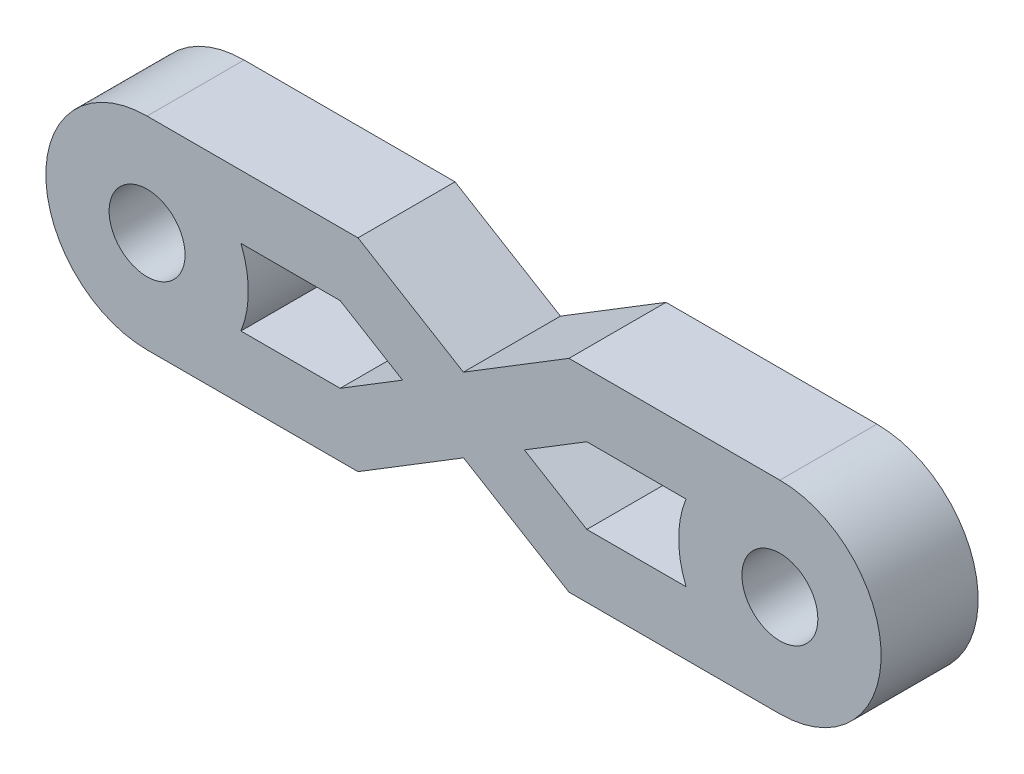
SolidWorks part; units mm, degrees
ref_plane "Front Plane" through (0, 0, 0) normal (0, 0, 1) x (1, 0, 0)
ref_plane "Top Plane" through (0, 0, 0) normal (0, 1, 0) x (1, 0, 0)
ref_plane "Right Plane" through (0, 0, 0) normal (1, 0, 0) x (0, 0, -1)
sketch "Sketch2" plane through (0, 0, 0) normal (0, 0, 1) x (1, 0, 0)
  line L0 (-117.2241, -4.8523) -> (-107.2241, -4.8523)
  line L1 (-87.2242, 4.8) -> (-97.2242, 4.8)
  line L2 (-97.2242, 4.8) -> (-102.2275, 1.7314)
  line L3 (-108.0708, -1.8523) -> (-112.7744, -1.8523)
  line L4 (-107.2241, -4.8523) -> (-102.2208, -1.7837)
  line L5 (-96.3775, 1.8) -> (-91.6739, 1.8)
  line L6 (-87.2242, -4.8) -> (-97.2242, -4.8)
  line L7 (-97.2242, -4.8) -> (-102.2208, -1.7837)
  line L8 (-108.0708, 1.7477) -> (-112.7744, 1.7477)
  line L9 (-117.2241, 4.7477) -> (-107.2241, 4.7477)
  line L10 (-107.2241, 4.7477) -> (-102.2275, 1.7314)
  line L11 (-96.3775, -1.8) -> (-91.6739, -1.8)
  line L12 (-99.3357, -0.0143) -> (-96.3775, 1.8)
  line L13 (-102.2208, -1.7837) -> (-99.3357, -0.0143) construction
  line L14 (-105.1126, -0.0381) -> (-108.0708, 1.7477)
  line L15 (-102.2208, -1.7837) -> (-105.1126, -0.0381) construction
  line L16 (-105.1126, -0.0381) -> (-108.0708, -1.8523)
  line L17 (-102.2275, 1.7314) -> (-105.1126, -0.0381) construction
  line L18 (-97.2242, -4.8) -> (-107.2241, -4.8523) construction
  line L19 (-99.3357, -0.0143) -> (-96.3775, -1.8)
  line L20 (-102.2275, 1.7314) -> (-99.3357, -0.0143) construction
  circle A0 centre (-117.2241, -0.0523) radius 1.8 construction
  circle A1 centre (-87.2242, 0) radius 1.8 construction
  circle A2 centre (-117.2241, -0.0523) radius 1.8
  circle A3 centre (-87.2242, 0) radius 1.8
  circle A4 centre (-117.2241, -0.0523) radius 4.8
  circle A5 centre (-87.2242, 0) radius 4.8
  point P21 (-96.121, -2.3361)
  circle M16 centre (-117.2241, -0.0523) radius 1.8
  circle M17 centre (-87.2242, 0) radius 1.8
  dimension "D1" = 3
  dimension "D2" = 3
  dimension "D3" = 3
  dimension "D4" = 3
extrude "Boss-Extrude1" add sketch "Sketch2" along normal up to surface (4.6 mm away) contours A4 M16 | A5 L1 L2 L10 L9 A4 L8 L14 L16 L3 L0 L4 L7 L6 L11 L19 L12 L5 | A5 M17 region at (-102.2241, -0.0262, 0) region at (-121.8883, -0.0523, 0) region at (-89.8316, -3.8674, 0)
